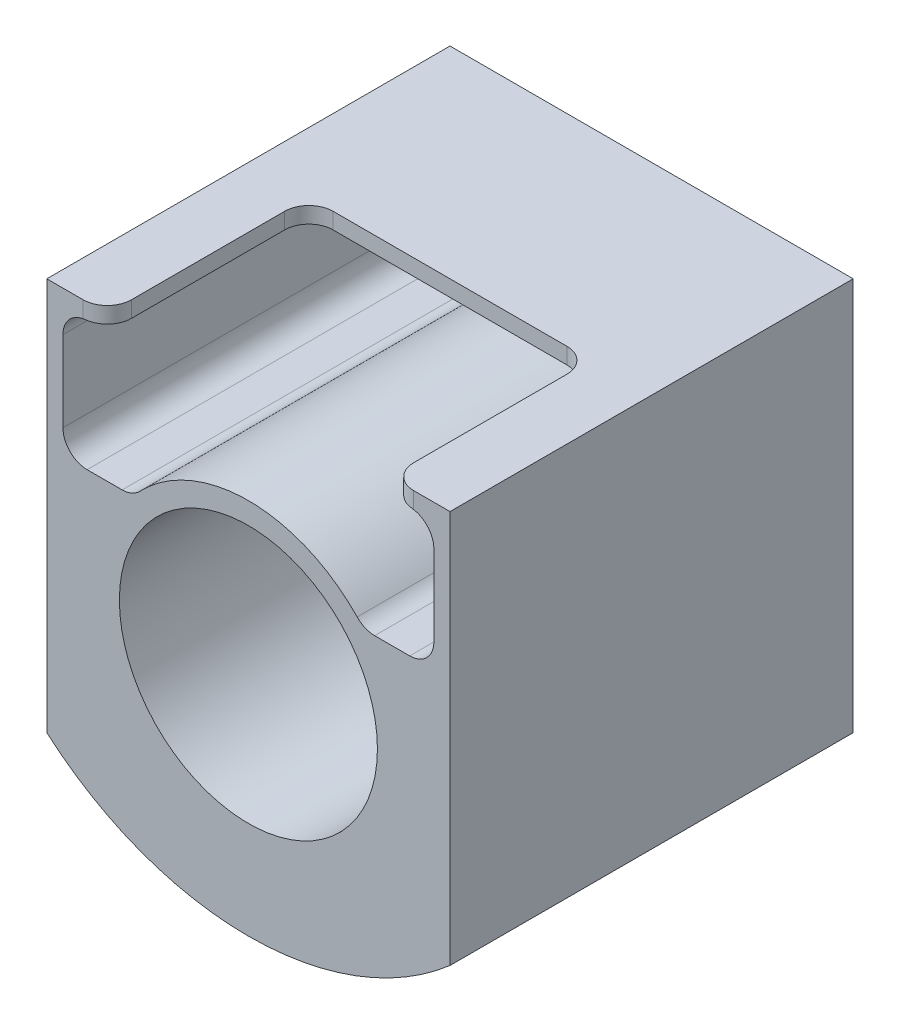
SolidWorks part; units mm, degrees
ref_plane "Front Plane" through (0, 0, 0) normal (0, 0, 1) x (1, 0, 0)
ref_plane "Top Plane" through (0, 0, 0) normal (0, 1, 0) x (1, 0, 0)
ref_plane "Right Plane" through (0, 0, 0) normal (1, 0, 0) x (0, 0, -1)
sketch "Sketch1" plane through (0, 0, 0) normal (0, 0, 1) x (1, 0, 0)
  line L1 (0, 0) -> (0, -38.1) construction
  line L2 (-25, 0) -> (-25, -28.7508)
  line L3 (25, 0) -> (25, -28.7508)
  line L4 (-25, 0) -> (-25, 20)
  line L5 (-25, 20) -> (25, 20)
  line L6 (25, 20) -> (25, 0)
  arc A0 (-25, -28.7508) -> (25, -28.7508) centre (0, 0) ccw
  dimension "D1" = 76.2
  dimension "D2" = 50
  dimension "D3" = 20
extrude "Boss-Extrude2" add sketch "Sketch1" along normal blind 50
sketch "Sketch2" plane through (0, 0, 50) normal (0, 0, 1) x (1, 0, 0)
  line L6 (0, 6) -> (0, -26) construction
  circle A0 centre (0, -10) radius 16
  dimension "D2" = 32
  dimension "D1" = 10
extrude "Cut-Extrude1" cut sketch "Sketch2" against normal through all both
sketch "Sketch4" plane through (0, 0, 50) normal (0, 0, 1) x (1, 0, 0)
  line L0 (-23, 18) -> (23, 18)
  line L3 (0, 20) -> (0, 6) construction
  line L4 (25, 20) -> (-25, 20) construction
  line L5 (23, 2) -> (14.3178, 2)
  line L6 (-23, 18) -> (-23, 2)
  line L7 (-23, 2) -> (-14.3178, 2)
  line L8 (-25, 20) -> (-25, -28.7508) construction
  line L9 (23, 18) -> (23, 2)
  circle A2 centre (0, -10) radius 16 construction
  arc A3 (14.3178, 2) -> (-14.3178, 2) centre (0, -10) ccw
  point P2 (0, 13)
  point P14 (0, 18)
  dimension "D1" = 37.3631
  dimension "D2" = 2
  dimension "D3" = 2
  dimension "D4" = 16
extrude "Cut-Extrude3" cut sketch "Sketch4" against normal through all
fillet "Fillet1" radius 3 6 edges at (23, 18, 25) (23, 2, 25) (14.3178, 2, 25) (-14.3178, 2, 25) (-23, 2, 25) (-23, 18, 25)
sketch "Sketch5" plane through (0, 20, 0) normal (0, 1, 0) x (1, 0, 0)
  line L0 (25, -50) -> (-25, -50) construction
  line L1 (-17.5, -50) -> (17.5, -50)
  line L2 (-17.5, -50) -> (-17.5, -25)
  line L3 (-17.5, -25) -> (17.5, -25)
  line L4 (17.5, -50) -> (17.5, -25)
  line L5 (0, 0) -> (0, -50) construction
  dimension "D1" = 35
  dimension "D2" = 25
extrude "Cut-Extrude4" cut sketch "Sketch5" against normal blind 10
fillet "Fillet2" radius 3 4 edges at (17.5, 19, 50) (17.5, 19, 25) (-17.5, 19, 25) (-17.5, 19, 50)
ref_plane "Plane1" through (0, 0, 14) normal (0, 0, 1) x (1, 0, 0)
sketch "Sketch6" plane through (0, 0, 14) normal (0, 0, 1) x (1, 0, 0)
  arc A0 (16, -10) -> (-16, -10) centre (0, -10) ccw
  circle A1 centre (0, -10) radius 16 construction
  arc A2 (16, -10) -> (-16, -10) centre (0, -10) cw
  circle A3 centre (0, -10) radius 9.5
  circle A4 centre (0, 3) radius 1.25
  circle A5 centre (13, -10) radius 1.25
  circle A6 centre (-13, -10) radius 1.25
  circle A7 centre (0, -23) radius 1.25
  point P15 (0, 0)
  point P16 (0, 0)
  point P17 (0, 0)
  point P18 (0, 0)
  dimension "D1" = 19
  dimension "D6" = 2.5
  dimension "D2" = 13
  dimension "D3" = 13
  dimension "D4" = 13
  dimension "D5" = 13
extrude "Boss-Extrude3" add sketch "Sketch6" against normal blind 5
sketch "Sketch7" plane through (0, 0, 0) normal (1, 0, 0) x (0, 0, -1)
  circle A0 centre (-40, -32) radius 2.5
  circle A1 centre (-10, -32) radius 2.5
  point P2 (0, 0)
  point P12 (0, 0)
  point P14 (0, 0)
  point P15 (0, 0)
  point P16 (0, 0)
  point P17 (0, 0)
  dimension "D3" = 5
  dimension "D1" = 32
  dimension "D2" = 10
  dimension "D4" = 30
extrude "Cut-Extrude5" cut sketch "Sketch7" against normal through all both and the other way through all
